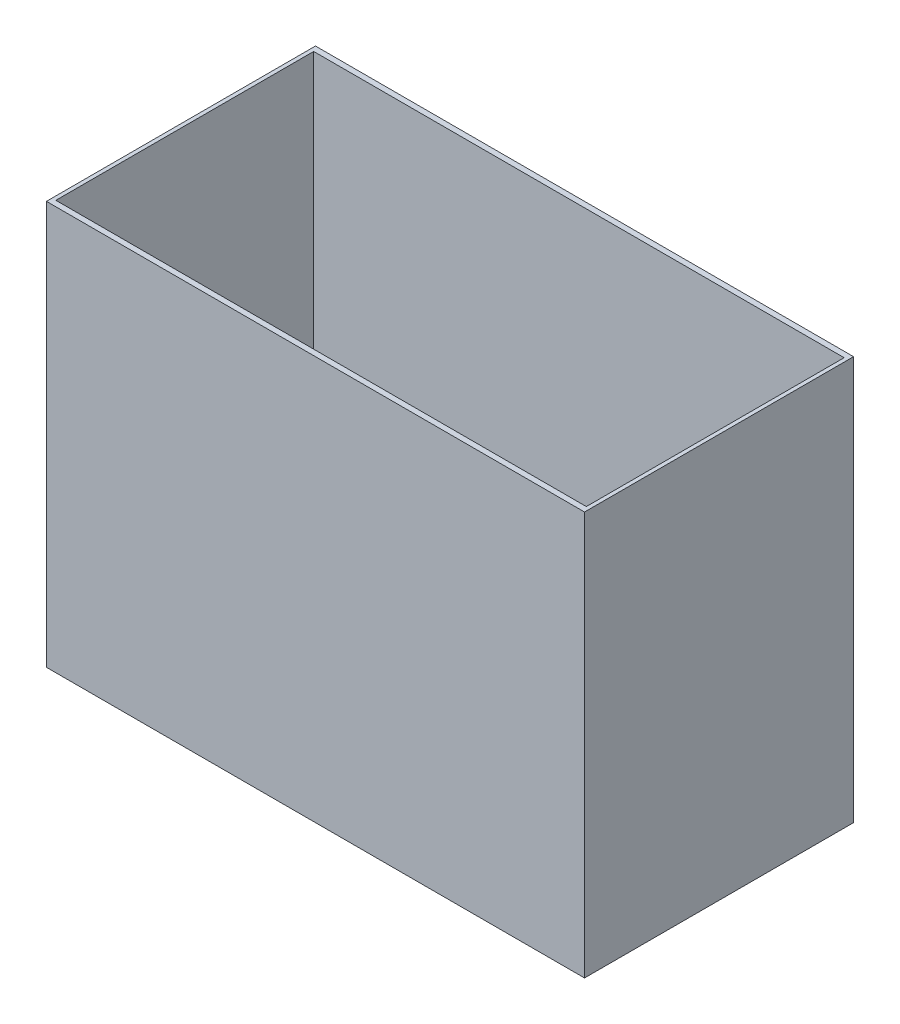
SolidWorks part; units mm, degrees
ref_plane "Front Plane" through (0, 0, 0) normal (0, 0, 1) x (1, 0, 0)
ref_plane "Top Plane" through (0, 0, 0) normal (0, 1, 0) x (1, 0, 0)
ref_plane "Right Plane" through (0, 0, 0) normal (1, 0, 0) x (0, 0, -1)
other "Bounding Box"
ref_plane "Default Plane" through (-292.1, 0, -139.7) normal (0, 1, 0) x (1, 0, 0)
sketch "Sketch1" plane through (0, 0, 0) normal (0, 1, 0) x (1, 0, 0)
  line L0 (-292.1, 0) -> (292.1, 0) construction
  line L1 (-292.1, 139.7) -> (292.1, 139.7)
  line L2 (-292.1, 139.7) -> (-292.1, -139.7)
  line L3 (-292.1, -139.7) -> (292.1, -139.7)
  line L4 (292.1, 139.7) -> (292.1, -139.7)
  line L5 (0, 139.7) -> (0, -139.7) construction
  point P8 (0, 0)
  dimension "D1" = 584.2
  dimension "D2" = 279.4
extrude "Boss-Extrude1" add sketch "Sketch1" along normal blind 12.7
sketch "Sketch2" plane through (0, 12.7, 0) normal (0, 1, 0) x (1, 0, 0)
  line L1 (-241.3, -107.95) -> (-152.4, -107.95)
  line L2 (-241.3, -107.95) -> (-241.3, -88.9)
  line L3 (-241.3, -88.9) -> (-152.4, -88.9)
  line L4 (-152.4, -107.95) -> (-152.4, -88.9)
  line L5 (-241.3, -107.95) -> (-152.4, -88.9) construction
  line L6 (-241.3, -88.9) -> (-152.4, -107.95) construction
  line L7 (-292.1, 139.7) -> (-292.1, -139.7) construction
  line L8 (-292.1, 0) -> (292.1, 0) construction
  line L9 (292.1, -139.7) -> (292.1, 139.7) construction
  line L10 (0, 0) -> (0, 121.6784) construction
  line L11 (241.3, -88.9) -> (152.4, -107.95) construction
  line L12 (241.3, -107.95) -> (152.4, -88.9) construction
  line L13 (152.4, -107.95) -> (152.4, -88.9)
  line L14 (241.3, -88.9) -> (152.4, -88.9)
  line L15 (241.3, -107.95) -> (241.3, -88.9)
  line L16 (241.3, -107.95) -> (152.4, -107.95)
  point P0 (-196.85, -98.425)
  point P17 (196.85, -98.425)
  dimension "D1" = 19.05
  dimension "D2" = 88.9
  dimension "D3" = 177.8
  dimension "D4" = 50.8
extrude "Boss-Extrude2" [suppressed] add sketch "Sketch2" along normal blind 304.8 separate body contours L2 L1 L4 L3
pattern_linear "LPattern1" [suppressed] count 2 spacing 304.8 of bodies 101
pattern_linear "LPattern2" [suppressed] count 2 spacing 215.9 of bodies 101
sketch "Sketch3" plane through (0, 0, 0) normal (0, 1, 0) x (1, 0, 0)
  line L1 (-304.8, -152.4) -> (304.8, -152.4)
  line L2 (-304.8, -152.4) -> (-304.8, 152.4)
  line L3 (-304.8, 152.4) -> (304.8, 152.4)
  line L4 (304.8, -152.4) -> (304.8, 152.4)
  line L5 (-304.8, -152.4) -> (304.8, 152.4) construction
  line L6 (-304.8, 152.4) -> (304.8, -152.4) construction
  line L7 (-300.482, -146.05) -> (300.482, -146.05)
  line L8 (-300.482, -146.05) -> (-300.482, 146.05)
  line L9 (-300.482, 146.05) -> (300.482, 146.05)
  line L10 (300.482, -146.05) -> (300.482, 146.05)
  line L11 (-300.482, -146.05) -> (300.482, 146.05) construction
  line L12 (-300.482, 146.05) -> (300.482, -146.05) construction
  point P0 (0, 0)
  point P6 (0, 0)
  dimension "D1" = 609.6
  dimension "D2" = 304.8
  dimension "D3" = 292.1
  dimension "D4" = 600.964
extrude "Boss-Extrude3" add sketch "Sketch3" along normal blind 457.2 separate body
